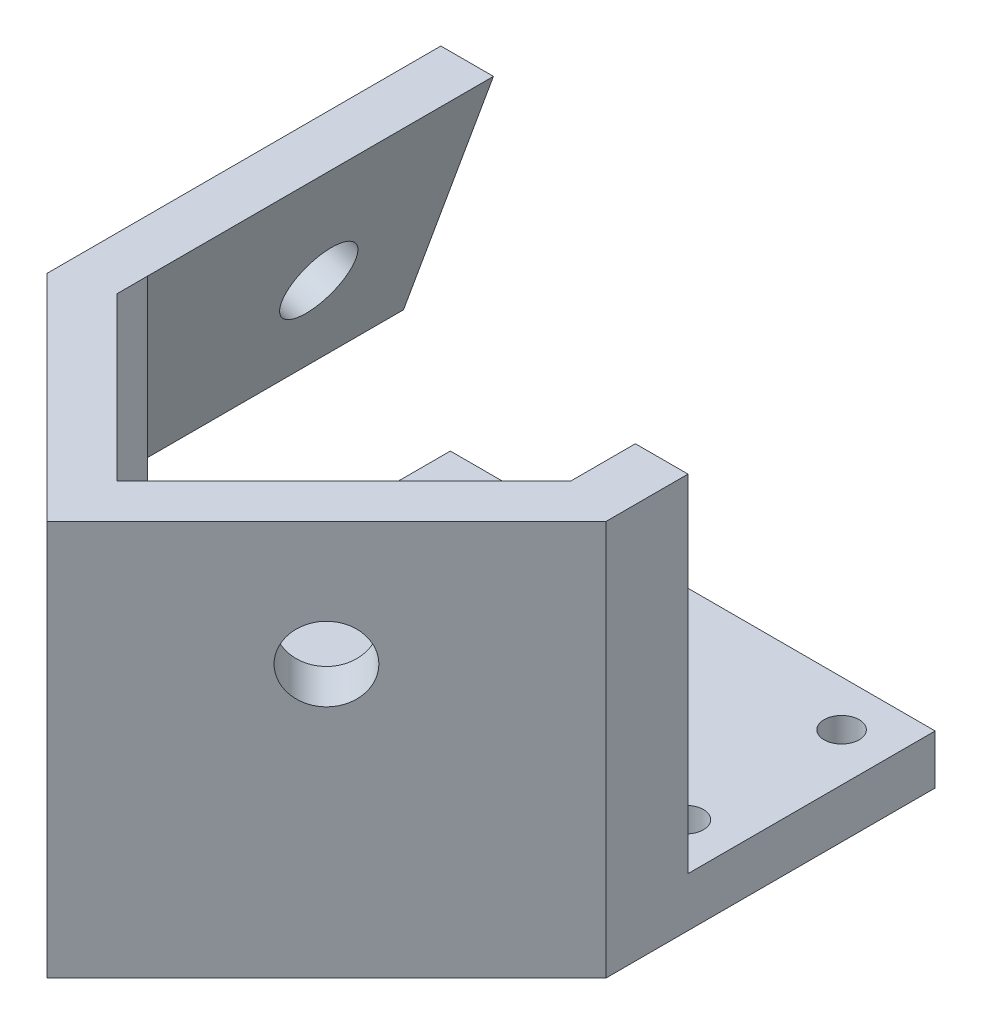
SolidWorks part; units mm, degrees
ref_plane "Front Plane" through (0, 0, 0) normal (0, 0, 1) x (1, 0, 0)
ref_plane "Top Plane" through (0, 0, 0) normal (0, 1, 0) x (1, 0, 0)
ref_plane "Right Plane" through (0, 0, 0) normal (1, 0, 0) x (0, 0, -1)
sketch "Sketch1" plane through (0, 0, 0) normal (0, 1, 0) x (1, 0, 0)
  line L0 (-35.921, 0) -> (0, 35.921)
  line L1 (-35.921, 0) -> (0, -35.921)
  line L2 (0, 35.921) -> (35.921, 0)
  line L3 (0, -35.921) -> (35.921, 0)
  line L4 (-35.921, 0) -> (35.921, 0) construction
  line L5 (0, 35.921) -> (0, -35.921) construction
  point P1 (0, 0)
  dimension "D1" = 50.8
  dimension "D2" = 50.8
extrude "Boss-Extrude1" add sketch "Sketch1" along normal mid plane 31.75
sketch "Sketch2" plane through (17.9605, 0, 17.9605) normal (0.7071, 0, 0.7071) x (0.7071, 0, -0.7071)
  circle A0 centre (0, 0) radius 4.7625
  dimension "D1" = 9.525
extrude "Cut-Extrude1" cut sketch "Sketch2" against normal blind 8
sketch "Sketch3" plane through (-17.9605, 0, 17.9605) normal (-0.7071, 0, 0.7071) x (0.7071, 0, 0.7071)
  circle A0 centre (0, 0) radius 4.7625
  dimension "D1" = 9.525
extrude "Cut-Extrude2" cut sketch "Sketch3" against normal blind 8
sketch "Sketch4" plane through (0, 15.875, 0) normal (0, 1, 0) x (1, 0, 0)
  line L0 (25.4, 10.521) -> (-25.4, 10.521)
  line L1 (35.921, 0) -> (0, 35.921) construction
  line L2 (0, 35.921) -> (-35.921, 0) construction
  line L3 (-25.4, 10.521) -> (0, 35.921)
  line L4 (0, 35.921) -> (25.4, 10.521)
  dimension "D1" = 25.4
extrude "Cut-Extrude3" cut sketch "Sketch4" against normal through all
sketch "Sketch5" plane through (0, 0, -10.521) normal (0, 0, -1) x (-1, 0, 0)
  line L0 (-35.921, 15.875) -> (-35.921, -15.875)
  line L1 (-35.921, -15.875) -> (39.135, -15.875)
  line L2 (39.135, -15.875) -> (27.579, 15.875)
  line L3 (27.579, 15.875) -> (-35.921, 15.875)
  line L4 (25.4, -15.875) -> (-25.4, -15.875) construction
  line L5 (-35.921, 15.875) -> (-35.921, -15.875) construction
  line L8 (25.4, 15.875) -> (-25.4, 15.875) construction
  point P6 (0, 0)
  dimension "D1" = 70
  dimension "D2" = 63.5
extrude "Boss-Extrude2" add sketch "Sketch5" against normal up to surface and the other way blind 31.75 up to face at (30.6605, 0, -5.2605)
sketch "Sketch6" plane through (-29.455, 10.7207, 0) normal (-0.9397, 0.342, 0) x (0, 0, 1)
  line L0 (-42.271, -28.3026) -> (-42.271, 5.4851) construction
  line L1 (-42.271, -28.3026) -> (-10.521, -28.3026) construction
  circle A0 centre (-26.396, -11.4088) radius 4.7625
  point P4 (-42.271, -11.4088)
  point P7 (-26.396, -28.3026)
  dimension "D1" = 9.525
extrude "Cut-Extrude4" cut sketch "Sketch6" against normal through all
sketch "Sketch7" plane through (0, 0, -42.271) normal (0, 0, -1) x (-1, 0, 0)
  line L1 (-35.921, -15.875) -> (39.135, -15.875) construction
  line L3 (20.8214, 15.875) -> (32.3775, -15.875)
  line L4 (-35.921, -15.875) -> (32.3775, -15.875)
  line L5 (39.135, -15.875) -> (27.579, 15.875) construction
  line L6 (27.579, 15.875) -> (-35.921, 15.875) construction
  line L7 (-35.921, -15.875) -> (-35.921, 15.875)
  line L8 (-35.921, 15.875) -> (20.8214, 15.875)
  dimension "D3" = 6.35
extrude "Cut-Extrude5" cut sketch "Sketch7" against normal blind 31.75
sketch "Sketch8" plane through (0, 15.875, 0) normal (0, 1, 0) x (1, 0, 0)
  line L5 (-42.1413, -6.2203) -> (-8.2965, -39.8855)
  line L6 (0, -35.921) -> (0, -57.0039)
  line L13 (0, -57.0039) -> (-46.5861, -10.6651)
  line L14 (-46.5861, -10.6651) -> (-42.1413, -6.2203)
  line L15 (-8.2965, -39.8855) -> (-8.2965, -27.6245)
  line L16 (-35.921, 0) -> (0, -35.921) construction
  line L17 (-8.2965, -27.6245) -> (0, -35.921)
  line L18 (-25.4, 10.521) -> (-35.921, 0) construction
extrude "Boss-Extrude3" [suppressed] add sketch "Sketch8" against normal up to surface (25.4 mm away) up to face at (2.1042, -15.875, 2.9758)
sketch "Sketch9" plane through (0, -15.875, 0) normal (0, -1, 0) x (1, 0, 0)
  line L0 (-25.4, -10.521) -> (-35.921, 0)
  line L1 (-35.921, 0) -> (-46.442, -10.521)
  line L2 (-46.442, -10.521) -> (-25.4, -10.521)
  line L3 (-35.921, 0) -> (0, 35.921) construction
extrude "Boss-Extrude4" add sketch "Sketch9" against normal up to surface (31.75 mm away) up to face at (-9.5866, 15.875, -10.0783)
sketch "Sketch10" plane through (0, 0, -42.271) normal (0, 0, -1) x (-1, 0, 0)
  line L0 (39.135, -15.875) -> (27.579, 15.875) construction
  line L1 (39.135, -15.875) -> (27.579, 15.875)
  line L6 (27.579, 15.875) -> (39.135, -15.875)
  line L7 (39.135, -15.875) -> (46.442, -15.875)
  line L8 (46.442, -15.875) -> (46.442, 15.875)
  line L9 (46.442, 15.875) -> (27.579, 15.875)
  line L10 (27.579, 15.875) -> (39.135, -15.875)
  line L11 (39.135, -15.875) -> (46.442, -15.875)
  line L12 (46.442, -15.875) -> (46.442, 15.875)
  line L13 (46.442, 15.875) -> (27.579, 15.875)
  line M7 (39.135, -15.875) -> (27.579, 15.875)
  dimension "D1" = 0
extrude "Cut-Extrude6" cut sketch "Sketch10" against normal through all contours L12 L13 L11 M7 region at (-39.4743, 2.3367, -42.271)
sketch "Sketch11" plane through (0, -15.875, 0) normal (0, -1, 0) x (1, 0, 0)
  line L3 (-32.3775, -10.521) -> (-39.135, -10.521)
  line L4 (-39.135, -42.271) -> (-39.135, -3.214) construction
  line L5 (-39.135, -10.521) -> (-39.135, -3.214)
  line L10 (0, 35.921) -> (-39.135, -3.214)
  line L11 (-39.135, -3.214) -> (-39.135, -42.271)
  line L12 (-39.135, -42.271) -> (-32.3775, -42.271)
  line L13 (-32.3775, -42.271) -> (-32.3775, -10.521)
  line L21 (-32.3775, -10.521) -> (35.921, -10.521)
  line L22 (35.921, -10.521) -> (35.921, 0)
  line L23 (35.921, 0) -> (0, 35.921)
  line L24 (0, 35.921) -> (-39.135, -3.214)
  line L29 (-32.3775, -10.521) -> (35.921, -10.521)
  line L30 (35.921, -10.521) -> (35.921, 0)
  line L31 (35.921, 0) -> (0, 35.921)
  dimension "D1" = 0
extrude "Boss-Extrude5" add sketch "Sketch11" along normal blind 12.7
sketch "Sketch12" plane through (0, -28.575, 0) normal (0, -1, 0) x (1, 0, 0)
  line L0 (35.921, -10.521) -> (35.921, 0)
  line L1 (35.921, 0) -> (0, 35.921)
  line L2 (0, 35.921) -> (-39.135, -3.214)
  line L3 (-39.135, -3.214) -> (-39.135, -42.271)
  line L4 (-39.135, -42.271) -> (35.921, -42.271)
  line L5 (35.921, -42.271) -> (35.921, -10.521)
extrude "Boss-Extrude6" add sketch "Sketch12" along normal blind 6.35
sketch "Sketch14" plane through (0, 0, -10.521) normal (0, 0, -1) x (-1, 0, 0)
  line L0 (36.9999, -28.575) -> (20.8214, 15.875)
  line L1 (39.135, -34.925) -> (26.3581, -34.925)
  line L2 (20.8214, 15.875) -> (10.1797, 15.875)
  line L3 (26.3581, -28.575) -> (10.1797, 15.875)
  line L4 (20.8214, 15.875) -> (-35.921, 15.875) construction
  line L5 (32.3775, -15.875) -> (20.8214, 15.875) construction
  line L6 (39.135, -34.925) -> (-35.921, -34.925) construction
  line L7 (39.135, -34.925) -> (39.135, -28.575)
  line L8 (39.135, -28.575) -> (36.9999, -28.575)
  line L9 (26.3581, -28.575) -> (26.3581, -34.925)
  line L11 (39.135, -28.575) -> (-35.921, -28.575) construction
  dimension "D1" = 10
extrude "Cut-Extrude7" cut sketch "Sketch14" along normal through all
sketch "Sketch15" plane through (0, -34.925, 0) normal (0, -1, 0) x (1, 0, 0)
  line L0 (-26.3581, -42.271) -> (35.921, -42.271) construction
  line L1 (29.7814, -16.396) -> (-20.2186, -16.396) construction
  line L2 (29.7814, -16.396) -> (29.7814, -36.396) construction
  line L3 (29.7814, -36.396) -> (-20.2186, -36.396) construction
  line L4 (-20.2186, -16.396) -> (-20.2186, -36.396) construction
  line L5 (29.7814, -16.396) -> (-20.2186, -36.396) construction
  line L6 (29.7814, -36.396) -> (-20.2186, -16.396) construction
  line L9 (-26.3581, -42.271) -> (-26.3581, -10.521) construction
  circle A0 centre (29.7814, -36.396) radius 2.25
  circle A1 centre (29.7814, -16.396) radius 2.25
  circle A2 centre (-20.2186, -16.396) radius 2.25
  circle A3 centre (-20.2186, -36.396) radius 2.25
  point P0 (4.7814, -26.396)
  point P11 (4.7814, -42.271)
  point P14 (-26.3581, -26.396)
  dimension "D1" = 4.5
  dimension "D2" = 50
  dimension "D3" = 20
extrude "Cut-Extrude8" cut sketch "Sketch15" against normal up to next
sketch "Sketch17" plane through (0, 15.875, 0) normal (0, 1, 0) x (1, 0, 0)
  line L0 (-20.8214, 10.521) -> (-20.8214, -6.1193)
  line L1 (-20.8214, -6.1193) -> (0, -26.9408)
  line L2 (0, -26.9408) -> (29.1635, 2.2227)
  line L3 (29.1635, 2.2227) -> (29.1635, 10.521)
  line L4 (-20.8214, 10.521) -> (35.921, 10.521) construction
  line L5 (14.5817, -12.359) -> (19.0719, -16.8491) construction
  line L6 (0, -35.921) -> (35.921, 0) construction
  line L7 (-10.4107, -16.53) -> (-14.9009, -21.0202) construction
  line L8 (-27.579, -8.342) -> (0, -35.921) construction
  line L9 (29.1635, 10.521) -> (35.921, 10.521) construction
  line L10 (-20.8214, 10.521) -> (-27.579, 10.521) construction
  line L11 (-27.579, 42.271) -> (-27.579, -8.342) construction
  line L12 (-20.8214, 10.521) -> (29.1635, 10.521)
  dimension "D1" = 6.35
extrude "Cut-Extrude9" cut sketch "Sketch17" against normal up to surface (44.45 mm away) up to face at (-20.2186, -28.575, -34.146)
sketch "Sketch20" plane through (0, 0, -10.521) normal (0, 0, -1) x (-1, 0, 0)
  line L7 (32.3775, -15.875) -> (20.8214, 15.875)
  line L8 (20.8214, 15.875) -> (20.8214, -28.575)
  line L9 (20.8214, -28.575) -> (26.3581, -28.575)
  line L10 (26.3581, -28.575) -> (26.3581, -34.925)
  line L11 (26.3581, -34.925) -> (39.135, -34.925)
  line L12 (39.135, -34.925) -> (39.135, -15.875)
  line L13 (39.135, -15.875) -> (32.3775, -15.875)
  line L14 (32.3775, -15.875) -> (20.8214, 15.875)
  line L15 (20.8214, 15.875) -> (20.8214, -28.575)
  line L16 (20.8214, -28.575) -> (26.3581, -28.575)
  line L17 (26.3581, -28.575) -> (26.3581, -34.925)
  line L18 (26.3581, -34.925) -> (39.135, -34.925)
  line L19 (39.135, -34.925) -> (39.135, -15.875)
  line L20 (39.135, -15.875) -> (32.3775, -15.875)
  dimension "D1" = 0
extrude "Cut-Extrude10" cut sketch "Sketch20" against normal blind 12.7
sketch "Sketch21" plane through (0, 0, 2.179) normal (0, 0, -1) x (-1, 0, 0)
  line L0 (26.3581, -28.575) -> (26.3581, -34.925) construction
  line L1 (33.742, -34.925) -> (26.3581, -34.925)
  line L2 (33.742, -34.925) -> (33.742, -15.875)
  line L3 (33.742, -15.875) -> (26.3581, -15.875)
  line L4 (26.3581, -34.925) -> (26.3581, -15.875)
  line L5 (33.742, -15.875) -> (32.3775, -15.875) construction
extrude "Cut-Extrude11" cut sketch "Sketch21" against normal through all
